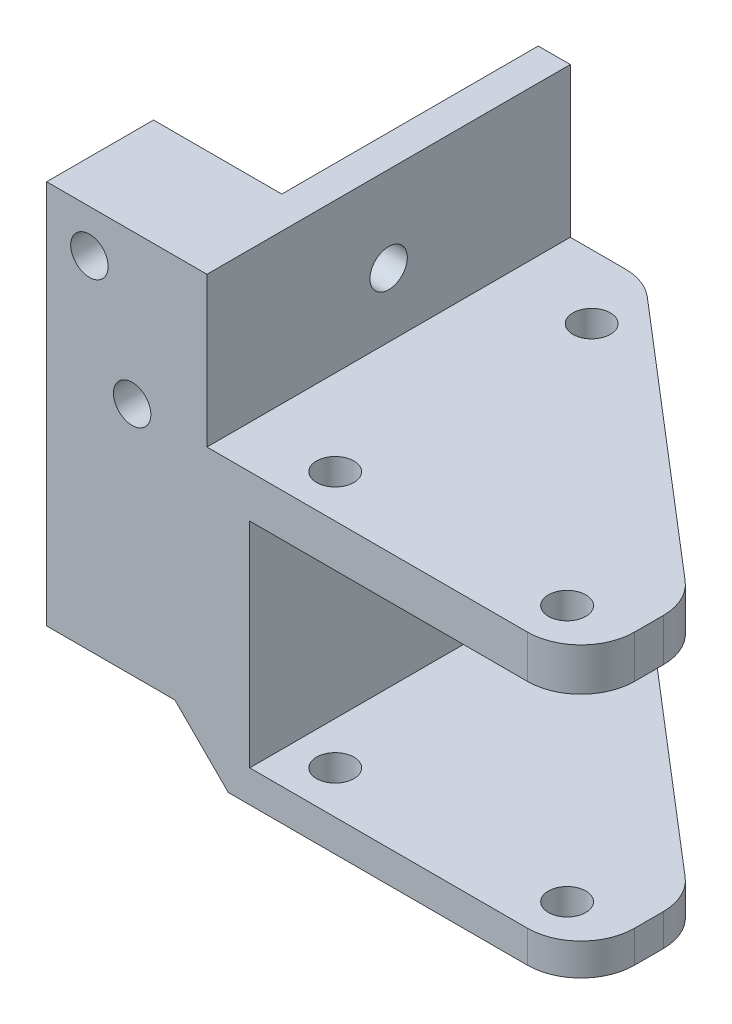
SolidWorks part; units mm, degrees
ref_plane "Płaszczyzna przednia" through (0, 0, 0) normal (0, 0, 1) x (1, 0, 0)
ref_plane "Płaszczyzna górna" through (0, 0, 0) normal (0, 1, 0) x (1, 0, 0)
ref_plane "Płaszczyzna prawa" through (0, 0, 0) normal (1, 0, 0) x (0, 0, -1)
sketch "Szkic1" plane through (0, 0, 0) normal (0, 0, 1) x (1, 0, 0)
  line L1 (-6, 9) -> (6, 9)
  line L2 (-6, 9) -> (-6, -9)
  line L3 (-6, -9) -> (6, -9)
  line L4 (6, 9) -> (6, -9)
  line L5 (-6, 9) -> (6, -9) construction
  line L6 (-6, -9) -> (6, 9) construction
  circle A0 centre (-2, 5) radius 1.75
  circle A1 centre (2, -5) radius 1.75
  point P0 (0, 0)
  dimension "D3" = 4
  dimension "D5" = 3.5
  dimension "D1" = 18
  dimension "D2" = 12
  dimension "D4" = 4
  dimension "D6" = 4
  dimension "D7" = 4
extrude "Dodanie-wyciągnięcie1" add sketch "Szkic1" along normal blind 5
sketch "Szkic2" plane through (0, 0, 5) normal (0, 0, 1) x (1, 0, 0)
  line L0 (-6, -27) -> (6, -27)
  line L4 (6, -9) -> (6, 9)
  line L5 (6, 9) -> (-6, 9)
  line L6 (-6, 9) -> (-6, -9)
  line L7 (-6, -9) -> (6, -9)
  line L8 (6, -27) -> (6, 9)
  line L9 (6, 9) -> (-6, 9)
  line L10 (-6, 9) -> (-6, -27)
  circle A1 centre (-2, 5) radius 1.75
  circle A2 centre (-2, 5) radius 1.75
  circle A3 centre (2, -5) radius 1.75
  circle A4 centre (2, -5) radius 1.75
  dimension "D4" = 36
  dimension "D1" = 0
  dimension "D2" = 0
  dimension "D3" = 0
extrude "Dodanie-wyciągnięcie2" add sketch "Szkic2" along normal blind 5
sketch "Szkic5" plane through (6, 0, 0) normal (1, 0, 0) x (0, 0, -1)
  line L0 (-10, -27) -> (-10, 9) construction
  line L1 (-10, -9) -> (24, -9)
  line L2 (-10, -9) -> (-10, -5)
  line L3 (-10, -5) -> (24, -5)
  line L4 (24, -9) -> (24, -5)
  dimension "D1" = 4
  dimension "D2" = 34
extrude "Dodanie-wyciągnięcie5" add sketch "Szkic5" along normal blind 38
sketch "Szkic6" plane through (0, -9, 0) normal (0, -1, 0) x (1, 0, 0)
  line L1 (6, -24) -> (13, -24)
  line L2 (6, -24) -> (6, 10)
  line L3 (6, 10) -> (13, 10)
  line L4 (13, -24) -> (13, 10)
  line L5 (44, 10) -> (6, 10) construction
  dimension "D1" = 34
  dimension "D2" = 7
extrude "Dodanie-wyciągnięcie6" add sketch "Szkic6" along normal up to surface (18 mm away) up to face at (0, -27, 7.5)
sketch "Szkic7" plane through (0, -5, 0) normal (0, 1, 0) x (1, 0, 0)
  line L0 (6, 0) -> (6, -10) construction
  line L1 (44, -10) -> (6, -10) construction
  circle A0 centre (17, -6) radius 1.75
  circle A1 centre (17, 18) radius 1.75
  circle A2 centre (38.7, -6) radius 1.75
  dimension "D1" = 21.7
  dimension "D2" = 3.5
  dimension "D3" = 11
  dimension "D4" = 24
  dimension "D5" = 4
extrude "Wytnij-wyciągnięcie1" cut sketch "Szkic7" against normal blind 4
sketch "Szkic8" plane through (0, -5, 0) normal (0, 1, 0) x (1, 0, 0)
  line L0 (16, 24) -> (44, 0)
  line L5 (6, 24) -> (6, 0)
  line L6 (6, 0) -> (6, -10)
  line L7 (6, -10) -> (44, -10)
  line L8 (44, -10) -> (44, 24)
  line L9 (44, 24) -> (6, 24)
  line L10 (6, 24) -> (6, 0)
  line L11 (6, 0) -> (6, -10)
  line L12 (6, -10) -> (44, -10)
  line L13 (44, -10) -> (44, 24)
  line L14 (44, 24) -> (6, 24)
  line M12 (44, -10) -> (44, 24)
  line M13 (44, 24) -> (6, 24)
  dimension "D2" = 10
  dimension "D3" = 10
  dimension "D1" = 0
extrude "Wytnij-wyciągnięcie2" cut sketch "Szkic8" against normal blind 4 contours L0 M13 M12 region at (34.6667, -5, -16)
fillet "Zaokrąglenie1" radius 5 3 edges at (16, -7, -24) (44, -7, 0) (44, -7, 10)
sketch "Szkic9" plane through (6, 0, 0) normal (-1, 0, 0) x (0, 0, 1)
  line L1 (5, -9) -> (0, -9)
  line L2 (5, -9) -> (5, -27)
  line L3 (5, -27) -> (0, -27)
  line L4 (0, -9) -> (0, -27)
  line L5 (-24, -27) -> (5, -27) construction
  dimension "D1" = 18
  dimension "D2" = 5
extrude "Dodanie-wyciągnięcie7" add sketch "Szkic9" along normal up to surface (12 mm away) up to face at (-6, -9, 5)
sketch "Szkic10" plane through (0, -27, 0) normal (0, -1, 0) x (1, 0, 0)
  line L0 (-6, 0) -> (6, 0) construction
  line L1 (6, -24) -> (6, 0) construction
  line L2 (-6, 0) -> (6, 0)
  line L3 (6, -24) -> (6, 0)
  line L4 (6, -5) -> (1, 0)
  line M3 (6, 0) -> (6, -24)
  dimension "D1" = 5
  dimension "D2" = 5
extrude "Dodanie-wyciągnięcie8" add sketch "Szkic10" against normal blind 18 contours L4 L2 M3 region at (4.3333, -27, -1.6667)
sketch "Szkic11" plane through (0, -27, 0) normal (0, -1, 0) x (1, 0, 0)
  line L1 (13, 10) -> (9, 10)
  line L2 (13, 10) -> (13, -24)
  line L3 (13, -24) -> (9, -24)
  line L4 (9, 10) -> (9, -24)
  line L5 (13, -24) -> (6, -24) construction
  dimension "D1" = 34
  dimension "D2" = 4
extrude "Dodanie-wyciągnięcie9" add sketch "Szkic11" along normal blind 2
sketch "Szkic12" plane through (0, -29, 0) normal (0, -1, 0) x (1, 0, 0)
  line L4 (13, -24) -> (13, 10)
  line L5 (13, 10) -> (9, 10)
  line L6 (9, 10) -> (9, -24)
  line L7 (9, -24) -> (13, -24)
  line L8 (13, -24) -> (13, 10)
  line L9 (13, 10) -> (9, 10)
  line L10 (9, 10) -> (9, -24)
  line L11 (9, -24) -> (13, -24)
  line L13 (13, -24) -> (14.1504, -24)
  line L14 (17.4043, -22.7963) -> (42.254, -1.4966)
  line L15 (44, 2.2997) -> (44, 5)
  line L16 (39, 10) -> (13, 10)
  line L17 (13, 10) -> (13, -24)
  line L18 (13, -24) -> (14.1504, -24)
  line L19 (17.4043, -22.7963) -> (42.254, -1.4966)
  line L20 (44, 2.2997) -> (44, 5)
  line L21 (39, 10) -> (13, 10)
  line L22 (13, 10) -> (13, -24)
  circle A0 centre (17, 6) radius 1.75 construction
  circle A1 centre (17, 6) radius 1.75
  circle A2 centre (17, -18) radius 1.75 construction
  arc A3 (14.1504, -24) -> (17.4043, -22.7963) centre (14.1504, -19) ccw
  arc A4 (42.254, -1.4966) -> (44, 2.2997) centre (39, 2.2997) ccw
  arc A5 (44, 5) -> (39, 10) centre (39, 5) ccw
  arc A6 (14.1504, -24) -> (17.4043, -22.7963) centre (14.1504, -19) ccw
  arc A7 (42.254, -1.4966) -> (44, 2.2997) centre (39, 2.2997) ccw
  arc A8 (44, 5) -> (39, 10) centre (39, 5) ccw
  circle A9 centre (17, -18) radius 1.75
  circle A10 centre (38.7, 6) radius 1.75 construction
  circle A11 centre (38.7, 6) radius 1.75
  line M13 (13, -24) -> (13, 10)
  line M14 (13, 10) -> (9, 10)
  line M15 (9, 10) -> (9, -24)
  line M16 (9, -24) -> (13, -24)
  dimension "D1" = 0
  dimension "D2" = 0
extrude "Dodanie-wyciągnięcie10" add sketch "Szkic12" along normal blind 3 contours L20 A8 L21 L18 A6 L19 A7 A11 A9 A1 M13 | M16 M13 M14 M15 region at (11, -29, -7) region at (25.5234, -29, -2.9045)
chamfer "Sfazowanie1" distance 3 angle 45 1 edges at (9, -27, -7)
chamfer "Sfazowanie2" distance 2 angle 45 1 edges at (9, -32, -7)
sketch "Szkic13" plane through (0, -5, 0) normal (0, 1, 0) x (1, 0, 0)
  line L1 (6, -10) -> (9, -10)
  line L2 (6, -10) -> (6, 24)
  line L3 (6, 24) -> (9, 24)
  line L4 (9, -10) -> (9, 24)
  line L6 (14.1504, 24) -> (6, 24) construction
  dimension "D1" = 34
  dimension "D2" = 3
extrude "Dodanie-wyciągnięcie11" add sketch "Szkic13" along normal up to surface (14 mm away) up to face at (0, 9, 5)
sketch "Szkic14" plane through (9, 0, 0) normal (1, 0, 0) x (0, 0, -1)
  line L0 (24, 9) -> (24, -5) construction
  line L1 (-10, -5) -> (24, -5) construction
  circle A0 centre (7, 1) radius 1.75
  dimension "D1" = 17
  dimension "D2" = 3.5
  dimension "D3" = 6
extrude "Wytnij-wyciągnięcie3" cut sketch "Szkic14" against normal blind 3
